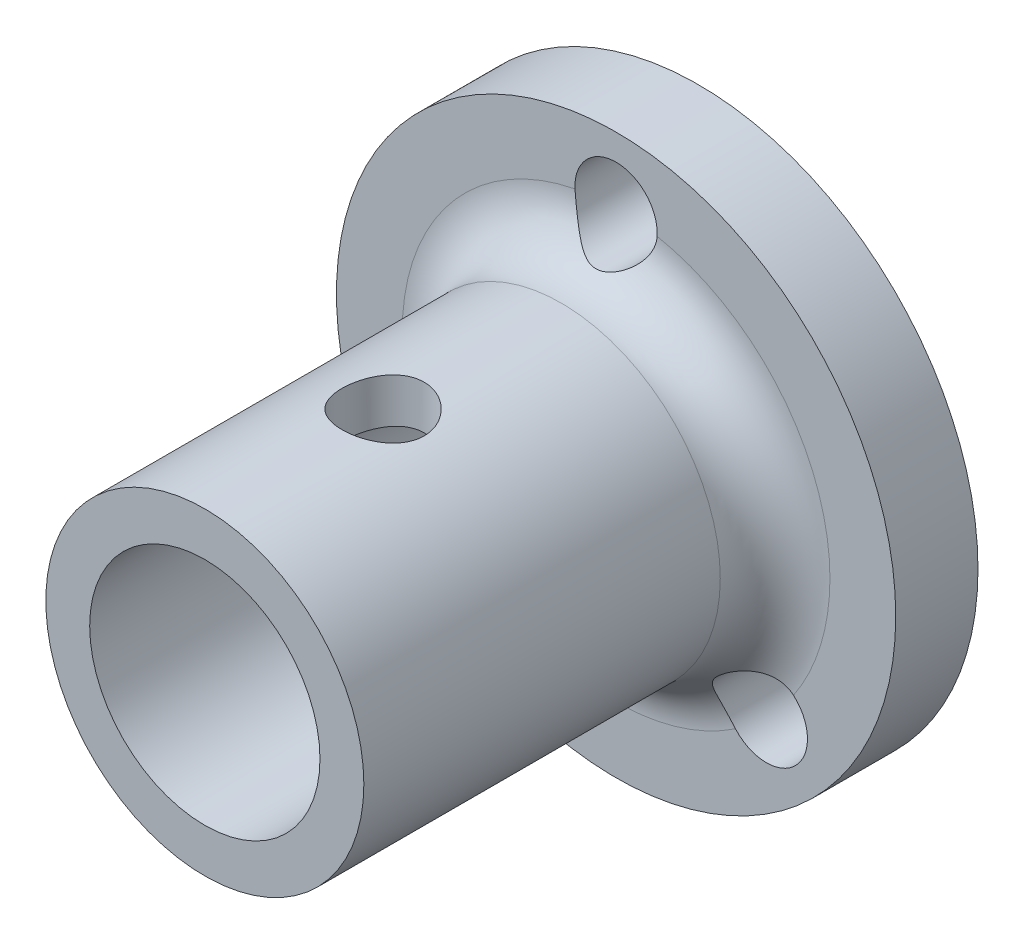
SolidWorks part; units mm, degrees
ref_plane "Front Plane" through (0, 0, 0) normal (0, 0, 1) x (1, 0, 0)
ref_plane "Top Plane" through (0, 0, 0) normal (0, 1, 0) x (1, 0, 0)
ref_plane "Right Plane" through (0, 0, 0) normal (1, 0, 0) x (0, 0, -1)
sketch "Эскиз1" plane through (0, 0, 0) normal (0, 0, 1) x (1, 0, 0)
  line L0 (-14.4715, 0) -> (29.092, 0) construction
  line L1 (0, 14.0862) -> (0, -21.8866) construction
  line L2 (-8.1733, -8.1733) -> (10.966, 10.966) construction
  circle A0 centre (0, 0) radius 4.2
  circle A1 centre (0, 0) radius 10.2
  circle A5 centre (0, 0) radius 7.75 construction
  circle A7 centre (0, 7.75) radius 1.5
  circle A10 centre (-5.4801, -5.4801) radius 1.5
  circle A11 centre (5.4801, -5.4801) radius 1.5
  dimension "D1" = 8.4
  dimension "D3" = 45
  dimension "D4" = 15.5
  dimension "D5" = 3
  dimension "D2" = 6
extrude "Бобышка-Вытянуть1" add sketch "Эскиз1" along normal mid plane 3
sketch "Эскиз2" plane through (0, 0, 1.5) normal (0, 0, 1) x (1, 0, 0)
  circle A0 centre (0, 0) radius 4.2 construction
  circle A1 centre (0, 0) radius 4.2
  circle A2 centre (0, 0) radius 5.8
  dimension "D1" = 1.6
extrude "Бобышка-Вытянуть2" add sketch "Эскиз2" along normal blind 15
fillet "Скругление1" radius 2 1 edges at (5.8, 0, 1.5)
sketch "Эскиз3" plane through (0, 0, 0) normal (0, 1, 0) x (1, 0, 0)
  line L0 (0, 0) -> (0, -13.8202) construction
  circle A0 centre (0, -10) radius 1.5
  dimension "D1" = 3
  dimension "D2" = 10
extrude "Вырез-Вытянуть1" cut sketch "Эскиз3" against normal through all both and the other way through all
